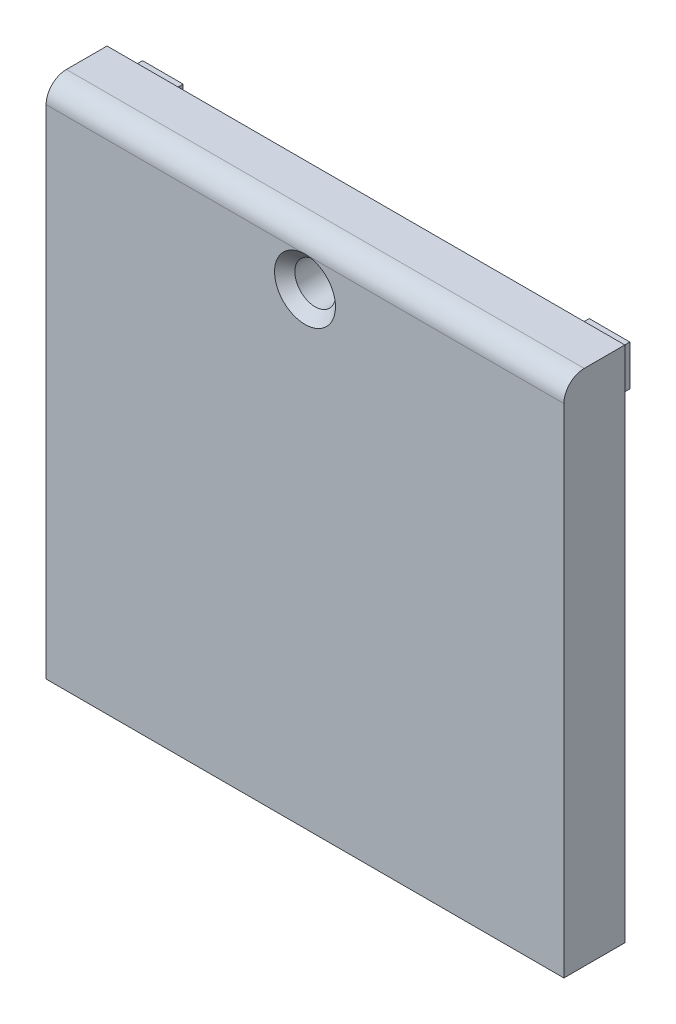
SolidWorks part; units mm, degrees
material "ABS"
ref_plane "Plano frontal" through (0, 0, 0) normal (0, 0, 1) x (1, 0, 0)
ref_plane "Plano superior" through (0, 0, 0) normal (0, 1, 0) x (1, 0, 0)
ref_plane "Plano direito" through (0, 0, 0) normal (1, 0, 0) x (0, 0, -1)
sketch "Esboço1" plane through (0, 0, 0) normal (0, 0, 1) x (1, 0, 0)
  line L1 (25.5, 25.5) -> (-25.5, 25.5)
  line L2 (25.5, 25.5) -> (25.5, -25.5)
  line L3 (25.5, -25.5) -> (-25.5, -25.5)
  line L4 (-25.5, 25.5) -> (-25.5, -25.5)
  line L5 (25.5, 25.5) -> (-25.5, -25.5) construction
  line L6 (25.5, -25.5) -> (-25.5, 25.5) construction
  point P0 (0, 0)
  dimension "D1" = 51
  dimension "D2" = 51
extrude "Ressalto-extrusão1" add sketch "Esboço1" along normal blind 6
sketch "Esboço2" plane through (0, 0, 0) normal (0, 0, -1) x (-1, 0, 0)
  line L0 (25.5, -25.5) -> (-25.5, -25.5) construction
  line L1 (-18.25, -16) -> (18.25, -16)
  line L2 (-18.25, -16) -> (-18.25, -22.5)
  line L3 (-18.25, -22.5) -> (18.25, -22.5)
  line L4 (18.25, -16) -> (18.25, -22.5)
  point P6 (0, -16)
  dimension "D1" = 36.5
  dimension "D2" = 6.5
  dimension "D3" = 3
extrude "Corte-extrusão1" cut sketch "Esboço2" against normal blind 4.5
sketch "Esboço3" plane through (0, 0, 6) normal (0, 0, 1) x (1, 0, 0)
  line L0 (25.5, 25.5) -> (-25.5, 25.5) construction
  circle A1 centre (0, 20.5) radius 2
  dimension "D1" = 4
  dimension "D2" = 5
extrude "Corte-extrusão2" cut sketch "Esboço3" against normal through all
sketch "Esboço4" plane through (0, 0, 0) normal (0, 0, -1) x (-1, 0, 0)
  line L0 (18.25, -16) -> (-18.25, -16) construction
  line L1 (-21, -10) -> (21, -10)
  line L2 (-21, -10) -> (-21, -13)
  line L3 (-21, -13) -> (21, -13)
  line L4 (21, -10) -> (21, -13)
  point P5 (0, -10)
  dimension "D1" = 3
  dimension "D2" = 3
  dimension "D3" = 42
extrude "Corte-extrusão3" cut sketch "Esboço4" against normal up to surface (4.5 mm away) up to face at (0, -19.25, 4.5)
pattern_linear "Padrão linear1" count 3 spacing 10 along (0, 1, 0) of "Corte-extrusão3"
fillet "Filete1" radius 2 1 edges at (0, 25.5, 6)
chamfer "Chanfro1" distance 1 angle 45 1 edges at (2, 20.5, 6)
sketch "Esboço5" plane through (0, 0, 0) normal (0, 0, -1) x (-1, 0, 0)
  line L0 (-25.5, -25.5) -> (-25.5, 25.5) construction
  line L1 (-24, 20) -> (-22, 20)
  line L2 (-24, 20) -> (-24, 24)
  line L3 (-24, 24) -> (-20, 24)
  line L4 (-20, 22) -> (-20, 24)
  line L5 (22, 20) -> (24, 20)
  line L6 (20, 22) -> (20, 24)
  line L7 (20, 24) -> (24, 24)
  line L8 (24, 20) -> (24, 24)
  line L11 (20, 22) -> (22, 22)
  line L12 (22, 20) -> (22, 22)
  line L15 (-20, 22) -> (-22, 22)
  line L16 (-22, 20) -> (-22, 22)
  line L17 (-25.5, 25.5) -> (25.5, 25.5) construction
  line L18 (25.5, 25.5) -> (25.5, -25.5) construction
  point P22 (-24, 22)
  point P24 (-22, 24)
  dimension "D1" = 1.5
  dimension "D2" = 1.5
  dimension "D3" = 4
  dimension "D4" = 1.5
  dimension "D5" = 4
extrude "Ressalto-extrusão2" add sketch "Esboço5" along normal blind 2
